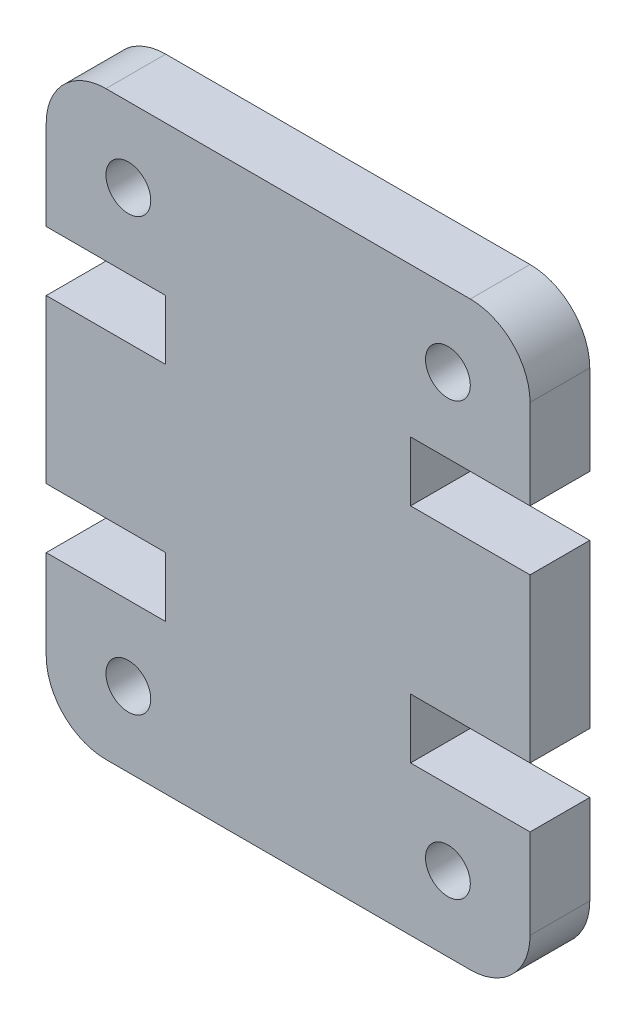
SolidWorks part; units mm, degrees
ref_plane "Front Plane" through (0, 0, 0) normal (0, 0, 1) x (1, 0, 0)
ref_plane "Top Plane" through (0, 0, 0) normal (0, 1, 0) x (1, 0, 0)
ref_plane "Right Plane" through (0, 0, 0) normal (1, 0, 0) x (0, 0, -1)
sketch "Sketch2" plane through (0, 0, 0) normal (0, 0, 1) x (1, 0, 0)
  line L0 (0, 7) -> (0, 12.455)
  line L1 (2, 0) -> (14.2, 0)
  line L2 (16.2, 5) -> (16.2, 2)
  line L3 (0, 9.7275) -> (16.2, 9.7275) construction
  line L4 (12.2, 5) -> (16.2, 5)
  line L5 (16.2, 7) -> (12.2, 7)
  line L6 (12.2, 7) -> (12.2, 5)
  line L7 (16.2, 7) -> (16.2, 12.455)
  line L8 (4, 7) -> (4, 5)
  line L9 (0, 14.455) -> (0, 17.455)
  line L10 (0, 7) -> (4, 7)
  line L11 (4, 5) -> (0, 5)
  line L12 (4, 14.455) -> (0, 14.455)
  line L13 (0, 12.455) -> (4, 12.455)
  line L14 (4, 12.455) -> (4, 14.455)
  line L15 (12.2, 12.455) -> (12.2, 14.455)
  line L16 (16.2, 12.455) -> (12.2, 12.455)
  line L17 (12.2, 14.455) -> (16.2, 14.455)
  line L18 (16.2, 14.455) -> (16.2, 17.455)
  line L19 (0, 5) -> (0, 2)
  line L20 (8.1, 19.455) -> (8.1, 0) construction
  line L21 (2, 19.455) -> (14.2, 19.455)
  circle A0 centre (13.45, 2.5) radius 0.75
  arc A1 (16.2, 2) -> (14.2, 0) centre (14.2, 2) cw
  circle A2 centre (2.75, 16.955) radius 0.75
  arc A3 (0, 2) -> (2, 0) centre (2, 2) ccw
  arc A4 (0, 17.455) -> (2, 19.455) centre (2, 17.455) cw
  circle A5 centre (2.75, 2.5) radius 0.75
  arc A6 (16.2, 17.455) -> (14.2, 19.455) centre (14.2, 17.455) ccw
  circle A7 centre (13.45, 16.955) radius 0.75
  point P18 (8.1, 9.7275)
  dimension "D1" = 1.5
  dimension "D2" = 2
  dimension "D3" = 2.75
  dimension "D4" = 8.1
  dimension "D5" = 2.5
  dimension "D6" = 5
  dimension "D8" = 9.7275
extrude "Boss-Extrude1" add sketch "Sketch2" along normal blind 4
sketch "Sketch3" plane through (0, 0, 4) normal (0, 0, 1) x (1, 0, 0)
  line L0 (0, 0) -> (16.2, 0)
  line L1 (16.2, 0) -> (16.2, 19.455)
  line L2 (16.2, 19.455) -> (0, 19.455)
  line L3 (0, 19.455) -> (0, 0)
extrude "Cut-Extrude1" cut sketch "Sketch3" against normal blind 2
equation "\"D4@Sketch2\"= \"fingerWidth@parametersSketch@prostheticParameters.SLDPRT\" / 2'Finger Width"
equation "\"D8@Sketch2\"= ( ( \"HL@parametersSketch@prostheticParameters.SLDPRT\" * 0.143 ) - 3 - 4 ) / 2 'MIP Length -SiliconeDIP-SiliconeMIP"
